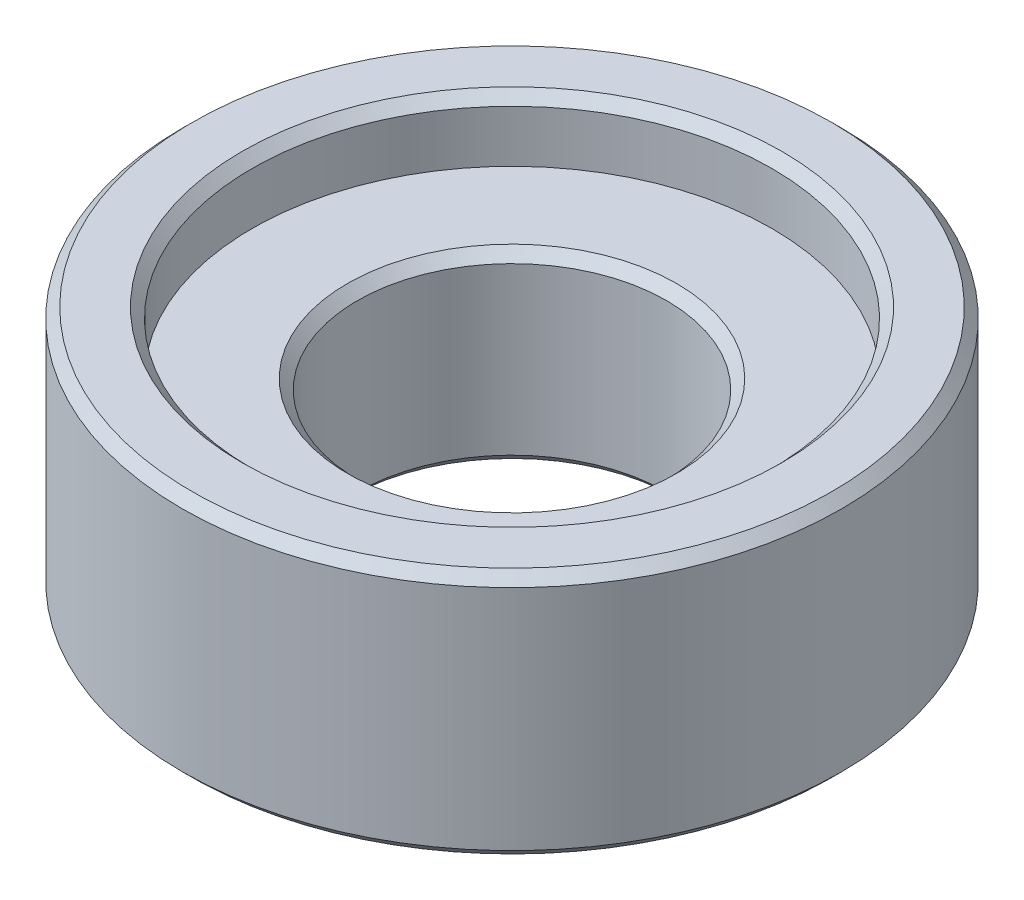
SolidWorks part; units mm, degrees
ref_plane "Front" through (0, 0, 0) normal (0, 0, 1) x (1, 0, 0)
ref_plane "Top" through (0, 0, 0) normal (0, 1, 0) x (1, 0, 0)
ref_plane "Right" through (0, 0, 0) normal (1, 0, 0) x (0, 0, -1)
sketch "Sketch1" plane through (0, 0, 0) normal (0, 0, 1) x (1, 0, 0)
  line L0 (16.4084, 12.7) -> (13.843, 12.7)
  line L1 (13.843, 12.7) -> (13.335, 12.192)
  line L2 (13.335, 12.192) -> (13.335, 9.525)
  line L3 (13.335, 9.525) -> (8.4455, 9.525)
  line L4 (8.4455, 9.525) -> (7.9375, 9.017)
  line L5 (7.9375, 9.017) -> (7.9375, 0.508)
  line L6 (7.9375, 0.508) -> (8.4455, 0)
  line L7 (8.4455, 0) -> (16.4084, 0)
  line L8 (16.4084, 0) -> (16.9164, 0.508)
  line L9 (16.9164, 0.508) -> (16.9164, 12.192)
  line L10 (16.9164, 12.192) -> (16.4084, 12.7)
  line L11 (0, 12.7) -> (0, 0) construction
revolve "Revolve1" add sketch "Sketch1" angle 360 about L11 reverse direction yes
